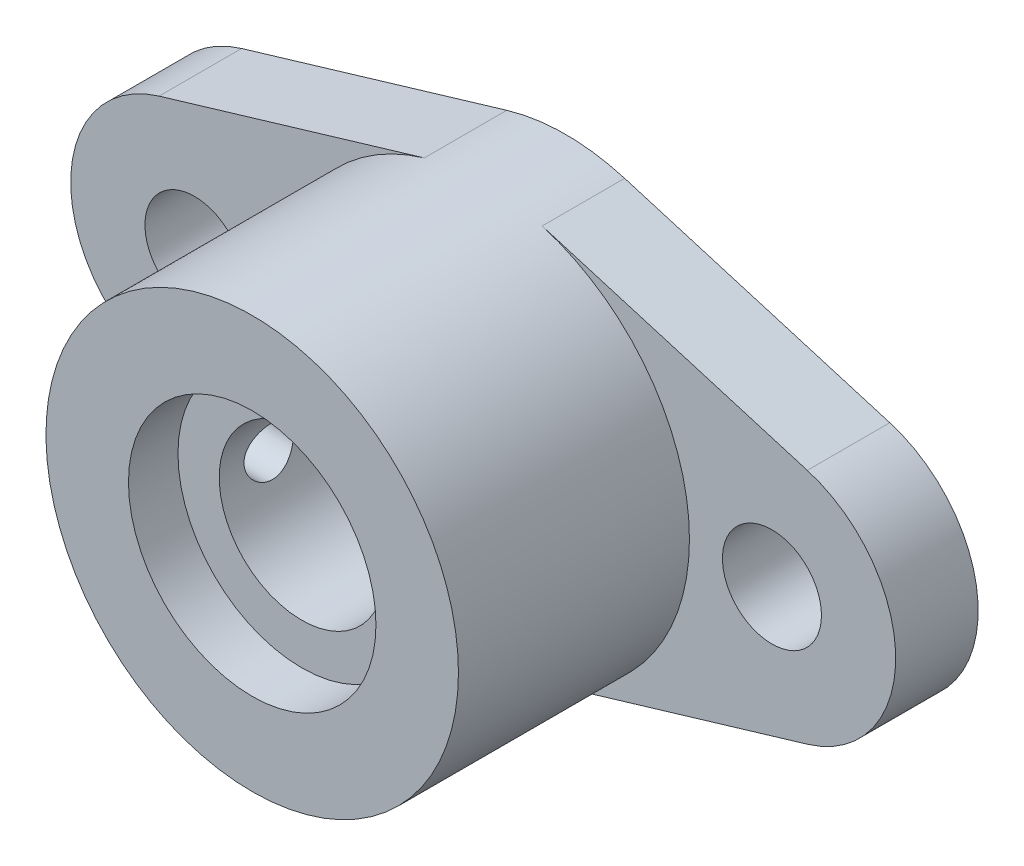
SolidWorks part; units mm, degrees
ref_plane "Front Plane" through (0, 0, 0) normal (0, 0, 1) x (1, 0, 0)
ref_plane "Top Plane" through (0, 0, 0) normal (0, 1, 0) x (1, 0, 0)
ref_plane "Right Plane" through (0, 0, 0) normal (1, 0, 0) x (0, 0, -1)
sketch "Sketch1" plane through (0, 0, 0) normal (0, 0, 1) x (1, 0, 0)
  line L0 (0, 0) -> (0, 31494.6299) construction
  line L1 (0, 0) -> (31494.6299, 0) construction
  line L2 (-39.2857, 14.3747) -> (-7.1429, 23.9579)
  line L3 (-39.2857, -14.3747) -> (-7.1429, -23.9579)
  line L4 (7.1429, -23.9579) -> (39.2857, -14.3747)
  line L5 (7.1429, 23.9579) -> (39.2857, 14.3747)
  circle A2 centre (0, 0) radius 25
  circle A3 centre (35, 0) radius 6
  circle A4 centre (-35, 0) radius 6
  arc A6 (39.2857, -14.3747) -> (39.2857, 14.3747) centre (35, 0) ccw
  arc A7 (-39.2857, 14.3747) -> (-39.2857, -14.3747) centre (-35, 0) ccw
  dimension "D1" = 50
  dimension "D2" = 12
  dimension "D3" = 12
  dimension "D6" = 30
  dimension "D7" = 30
  dimension "D4" = 35
  dimension "D5" = 35
extrude "Boss-Extrude1" add sketch "Sketch1" along normal blind 10 contours L2 A7 L3 A2 A4 | L4 A6 L5 A2 A3 region at (-23.0306, 18.5502, 0) region at (23.0306, 18.5502, 0)
extrude "Boss-Extrude2" add sketch "Sketch1<3>" along normal blind 38 contours A2 region at (0, 0, 0)
sketch "Sketch1<3>" plane through (0, 0, 0) normal (0, 0, 1) x (1, 0, 0) same geometry as "Sketch1"
hole_wizard "CBORE for M12 Hex Head Screw1" positions "Sketch2" profile "Sketch3" counterbore size "M12" standard "ISO" end condition through all
sketch "Sketch2" plane through (0, 0, 38) normal (0, 0, 1) x (1, 0, 0)
  point P0 (0, 0)
sketch "Sketch3" plane through (0, 0, 38) normal (1, 0, 0) x (0, -1, 0)
  line L0 (0, 0) -> (0, 38)
  line L1 (0, 38) -> (10, 38)
  line L3 (10, 38) -> (10, 6)
  line L4 (10, 6) -> (15, 6)
  line L5 (15, 6) -> (15, 0)
  line L7 (15, 0) -> (0, 0)
  line L11 (0, -6.35) -> (0, 107.95) construction
  dimension "Thru Hole Dia." = 20
  dimension "Thru Hole Depth" = 38
  dimension "C'Bore Dia." = 30
  dimension "C'Bore Depth" = 6
sketch "Sketch6" plane through (0, 0, 0) normal (1, 0, 0) x (0, 0, -1)
  line L0 (-38, 25) -> (-38, -25) construction
  line L1 (-38, -25) -> (0, -25) construction
  circle A0 centre (-26, 0) radius 3
  dimension "D1" = 6
  dimension "D2" = 12
  dimension "D3" = 25
extrude "Cut-Extrude1" cut sketch "Sketch6" against normal blind 38
